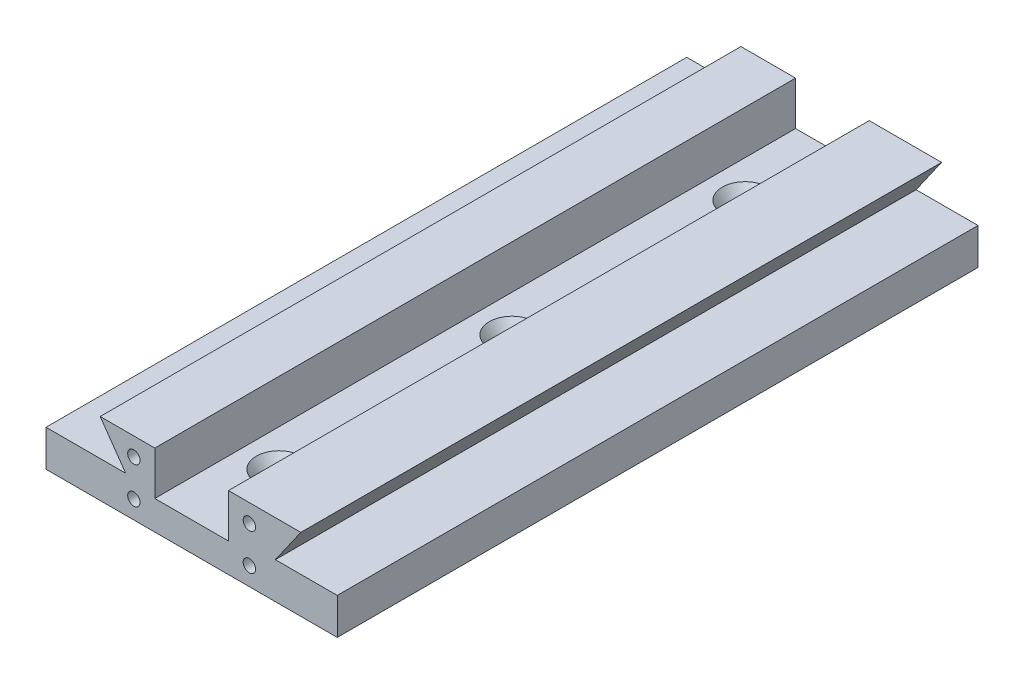
SolidWorks part; units mm, degrees
material "Ductile Iron"
ref_plane "Front Plane" through (0, 0, 0) normal (0, 0, 1) x (1, 0, 0)
ref_plane "Top Plane" through (0, 0, 0) normal (0, 1, 0) x (1, 0, 0)
ref_plane "Right Plane" through (0, 0, 0) normal (1, 0, 0) x (0, 0, -1)
sketch "dovetail-male-profile" plane through (0, 0, 0) normal (0, 0, 1) x (1, 0, 0)
  line L0 (0, 0) -> (127, 0)
  line L1 (127, 0) -> (127, 15.875)
  line L2 (127, 15.875) -> (100.0092, 15.875) construction
  line L3 (100.0092, 15.875) -> (111.125, 31.75)
  line L4 (111.125, 31.75) -> (15.875, 31.75) construction
  line L5 (15.875, 31.75) -> (26.9908, 15.875) construction
  line L6 (26.9908, 15.875) -> (0, 15.875)
  line L7 (0, 15.875) -> (0, 0)
  line L8 (111.125, 31.75) -> (23.6269, 31.75)
  line L10 (100.0092, 15.875) -> (127, 15.875)
  line L11 (23.6269, 31.75) -> (34.7427, 15.875)
  line L12 (34.7427, 15.875) -> (26.9908, 15.875)
  dimension "D1" = 127
  dimension "D2" = 55
  dimension "D3" = 95.25
  dimension "D4" = 55
  dimension "D5" = 31.75
  dimension "D6" = 15.875
  dimension "D7" = 6.35
extrude "x-guide-extrude" add sketch "dovetail-male-profile" along normal blind 279.4
sketch "Sketch1" plane through (0, 0, 0) normal (0, 0, 1) x (1, 0, 0)
  line L0 (47.4437, 31.75) -> (47.4437, 12.7)
  line L2 (47.4437, 12.7) -> (79.5563, 12.7)
  line L3 (79.5563, 12.7) -> (79.5563, 31.75)
  line L4 (63.5, 0) -> (63.5, 31.75) construction
  line L5 (111.125, 31.75) -> (23.6269, 31.75) construction
  line L6 (47.4437, 31.75) -> (79.5563, 31.75)
  line L7 (0, 0) -> (127, 0) construction
  circle A0 centre (63.5, 22.225) radius 18.669 construction
  point P12 (63.5, 0)
  dimension "D1" = 37.338
  dimension "D2" = 19.05
extrude "Cut-Extrude1" cut sketch "Sketch1" along normal through all contours L6 L0 L2 L3 region at (63.5, 22.225, 0)
hole_wizard "1/4-20 Tapped Hole1" positions "Sketch2" profile "Sketch3" tap size "1/4-20" standard "ANSI Inch"
sketch "Sketch2" plane through (0, 0, 0) normal (0, 0, -1) x (-1, 0, 0)
  line L0 (-63.5, 31.75) -> (-63.5, 0) construction
  line L3 (-103.3731, 15.875) -> (-34.7427, 15.875) construction
  line L5 (-29.1848, 23.8125) -> (-47.4437, 23.8125) construction
  line L6 (-88.6858, 23.8125) -> (-38.3142, 23.8125) construction
  line L7 (-88.6858, 23.8125) -> (-88.6858, 7.9375) construction
  line L8 (-88.6858, 7.9375) -> (-38.3142, 7.9375) construction
  line L9 (-38.3142, 23.8125) -> (-38.3142, 7.9375) construction
  point P0 (-88.6858, 23.8125)
  point P1 (-88.6858, 7.9375)
  point P2 (-38.3142, 7.9375)
  point P3 (-38.3142, 23.8125)
sketch "Sketch3" plane through (88.6858, 23.8125, 0) normal (1, 0, 0) x (0, 1, 0)
  line L0 (0, 0) -> (0, 18.0438)
  line L1 (0, 18.0438) -> (2.5527, 16.51)
  line L2 (2.5527, 16.51) -> (2.5527, 0)
  line L3 (2.5527, 0) -> (0, 0)
  line L4 (0, 18.0438) -> (-2.5527, 16.51) construction
  line L5 (0, -6.35) -> (0, 107.95) construction
  dimension "Tap Drill Dia." = 5.1054
  dimension "Tap Drill Depth" = 16.51
  dimension "Drill Angle" = 118
cosmetic thread "Hole Thread1" parameters "D1"=12.7, "D2"=6.35
cosmetic thread "Hole Thread2" parameters "D1"=12.7, "D2"=6.35
cosmetic thread "Hole Thread3" parameters "D1"=12.7, "D2"=6.35
cosmetic thread "Hole Thread4" parameters "D1"=12.7, "D2"=6.35
hole_wizard "1/4-28 Tapped Hole1" positions "Sketch4" profile "Sketch5" tap size "1/4-28" standard "ANSI Inch"
sketch "Sketch4" plane through (0, 0, 279.4) normal (0, 0, 1) x (1, 0, 0)
  point P0 (38.3142, 23.8125)
  point P1 (38.3142, 7.9375)
  point P2 (88.6858, 7.9375)
  point P3 (88.6858, 23.8125)
sketch "Sketch5" plane through (38.3142, 23.8125, 279.4) normal (1, 0, 0) x (0, -1, 0)
  line L0 (0, 0) -> (0, 18.1354)
  line L1 (0, 18.1354) -> (2.7051, 16.51)
  line L2 (2.7051, 16.51) -> (2.7051, 0)
  line L3 (2.7051, 0) -> (0, 0)
  line L4 (0, 18.1354) -> (-2.7051, 16.51) construction
  line L5 (0, -6.35) -> (0, 107.95) construction
  dimension "Tap Drill Dia." = 5.4102
  dimension "Tap Drill Depth" = 16.51
  dimension "Drill Angle" = 118
cosmetic thread "Hole Thread5" parameters "D1"=12.7, "D2"=6.35
cosmetic thread "Hole Thread6" parameters "D1"=12.7, "D2"=6.35
cosmetic thread "Hole Thread7" parameters "D1"=12.7, "D2"=6.35
cosmetic thread "Hole Thread8" parameters "D1"=12.7, "D2"=6.35
hole_wizard "bed mount CSK for 3/8 Flat Head Socket Cap Screw1" positions "Sketch7" profile "Sketch6" countersink size "3/8" standard "ANSI Inch" end condition up to next
sketch "Sketch7" plane through (0, 12.7, 0) normal (0, 1, 0) x (1, 0, 0)
  line L0 (63.5, -279.4) -> (63.5, 0) construction
  line L1 (47.4437, -279.4) -> (79.5563, -279.4) construction
  line L2 (47.4437, 0) -> (79.5563, 0) construction
  point P0 (63.5, -38.1)
  point P2 (63.5, -139.7)
  point P4 (63.5, -241.3)
  dimension "D1" = 101.6
  dimension "D2" = 101.6
sketch "Sketch6" plane through (63.5, 12.7, 38.1) normal (1, 0, 0) x (0, 0, 1)
  line L0 (0, 0) -> (0, 12.7)
  line L1 (0, 12.7) -> (5.0419, 12.7)
  line L2 (5.0419, 12.7) -> (5.0419, 5.6101)
  line L3 (5.0419, 5.6101) -> (9.9187, 0)
  line L5 (9.9187, 0) -> (0, 0)
  line L6 (-5.0419, 5.6101) -> (-9.9187, 0) construction
  line L11 (0, -6.35) -> (0, 107.95) construction
  dimension "Thru Hole Dia." = 10.0838
  dimension "Thru Hole Depth" = 12.7
  dimension "Near C'Sink Dia." = 19.8374
  dimension "Near C'Sink Angle" = 82
equation "\"dovetail-angle\" = 55"
equation "\"dovetail-stock-width\" = 5"
equation "\"dovetail-stock-height\" = 1.25"
equation "\"D1@dovetail-male-profile\"=\"dovetail-stock-width\""
equation "\"dovetail-throat-width\" = \"dovetail-stock-width\" - (2 * \"dovetail-depth\")"
equation "\"D3@dovetail-male-profile\"=\"dovetail-throat-width\""
equation "\"dovetail-depth\" = 0.5 * \"dovetail-stock-height\""
equation "\"D2@dovetail-male-profile\"=\"dovetail-angle\""
equation "\"D4@dovetail-male-profile\"=\"dovetail-angle\""
equation "\"D5@dovetail-male-profile\"=\"dovetail-stock-height\""
equation "\"D6@dovetail-male-profile\"=\"dovetail-depth\""
equation "\"delta-x\" = 6"
equation "\"delta-y\" = 3"
equation "\"gib-thickness\" = 0.25"
equation "\"x-slide-length\" = \"dovetail-stock-width\" + \"delta-x\""
equation "\"y-slide-length\" = \"dovetail-stock-width\" + \"delta-y\""
equation "\"D1@x-guide-extrude\"=\"x-slide-length\""
equation "\"D7@dovetail-male-profile\"=\"gib-thickness\""
equation "\"dog-point-diam\" = .149"
equation "\"dog-point-length\" = .067"
equation "\"dovetail-double-height\" = 2 * \"dovetail-depth\" + 0.5"
equation "\"acme-major-diam\" = .5"
equation "\"acme-pitch-diam\" = 0.45"
equation "\"acme-minor-diam\" = 0.4"
equation "\"acme-nut-od\" = 1.47"
equation "\"acme-nut-length\" = 1"
equation "\"acme-nut-trim-height\" = .75"
equation "\"screw-bearing-od\" = 0.5"
equation "\"screw-bearing-length\" = .25"
equation "\"end-plate-thickness\" = \"screw-bearing-length\""
equation "\"D1@Sketch1\"=\"acme-nut-od\""
equation "\"D2@Sketch1\"=\"acme-nut-trim-height\""
equation "\"screw-bearing-id\" = .375"
equation "\"screw-add-length\" = 2 * \"end-plate-thickness\" + 1 + 0.5"
equation "\"acme-nut-mount-hole-space-horz\" = 0.82"
equation "\"acme-nut-mount-hole-space-vert\" = 0.5 * \"acme-nut-length\""
equation "\"x-screw-length\" = \"x-slide-length\" + \"screw-add-length\""
equation "\"y-screw-length\" = \"y-slide-length\" + \"screw-add-length\""
